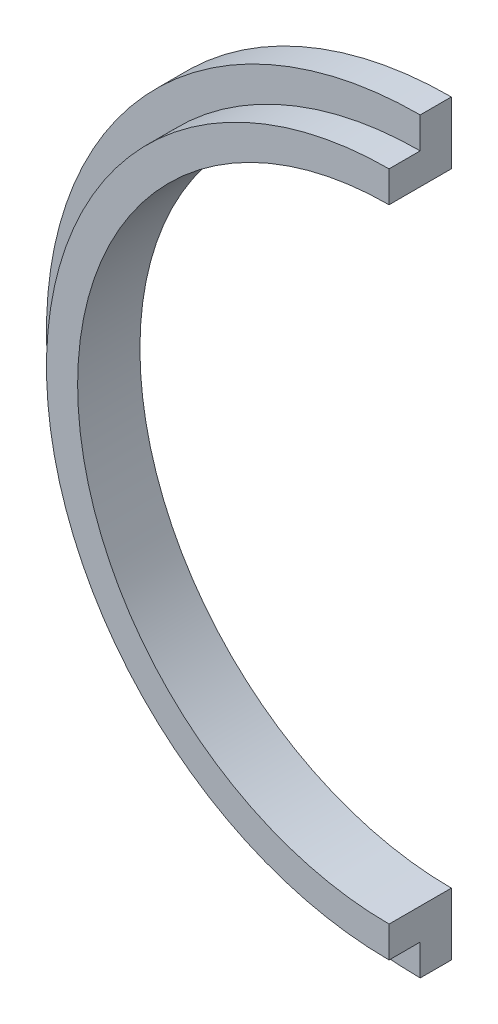
SolidWorks part; units mm, degrees
material "6061-T6 (SS)"
ref_plane "Alzado" through (0, 0, 0) normal (0, 0, 1) x (1, 0, 0)
ref_plane "Planta" through (0, 0, 0) normal (0, 1, 0) x (1, 0, 0)
ref_plane "Vista lateral" through (0, 0, 0) normal (1, 0, 0) x (0, 0, -1)
sketch "Sketch1" plane through (0, 0, 0) normal (0, 0, 1) x (1, 0, 0)
  circle A0 centre (0, 0) radius 180
  circle A1 centre (0, 0) radius 150
  dimension "D1" = 360
  dimension "D2" = 30
extrude "Boss-Extrude1" add sketch "Sketch1" along normal blind 15
sketch "Sketch2" plane through (0, 0, 15) normal (0, 0, 1) x (1, 0, 0)
  circle A0 centre (0, 0) radius 150
  circle A1 centre (0, 0) radius 165
  circle A2 centre (0, 0) radius 150 construction
  dimension "D1" = 15
extrude "Boss-Extrude2" add sketch "Sketch2" along normal blind 15
sketch "Sketch3" plane through (0, 0, 0) normal (0, 0, 1) x (1, 0, 0)
  line L0 (0, 180) -> (0, -180)
  line L1 (0, -180) -> (245, -180)
  line L2 (245, -180) -> (245, 180)
  line L3 (245, 180) -> (0, 180)
  circle A0 centre (0, 0) radius 180 construction
  dimension "D1" = 245
extrude "Cut-Extrude1" cut sketch "Sketch3" along normal up to next
